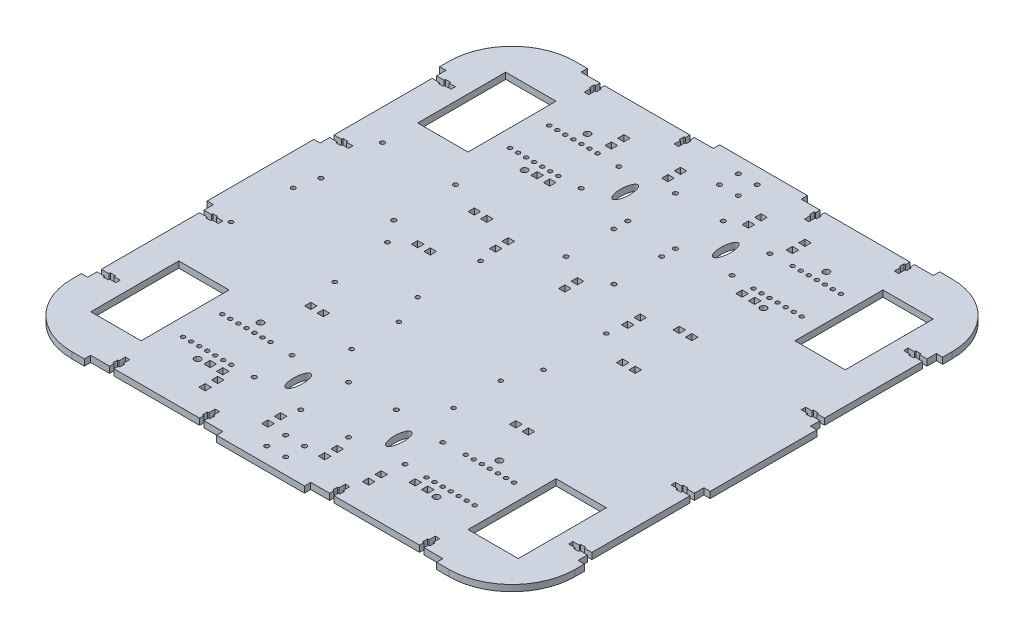
SolidWorks part; units mm, degrees
ref_plane "Front Plane" through (0, 0, 0) normal (0, 0, 1) x (1, 0, 0)
ref_plane "Top Plane" through (0, 0, 0) normal (0, 1, 0) x (1, 0, 0)
ref_plane "Right Plane" through (0, 0, 0) normal (1, 0, 0) x (0, 0, -1)
sketch "Sketch1" plane through (0, 0, 0) normal (0, 1, 0) x (1, 0, 0)
  line L0 (0, -1000) -> (0, 49000) construction
  line L1 (-170, 165) -> (-130, 165)
  line L2 (-170, 165) -> (-170, 95)
  line L3 (-170, 95) -> (-130, 95)
  line L4 (-130, 165) -> (-130, 95)
  line L5 (170, 95) -> (130, 95)
  line L6 (130, 165) -> (130, 95)
  line L7 (170, 165) -> (130, 165)
  line L8 (170, 165) -> (170, 95)
  line L9 (-1000, 0) -> (49000, 0) construction
  line L10 (-10, 190) -> (10, 190)
  line L11 (-10, 190) -> (-10, 170)
  line L12 (-10, 170) -> (10, 170)
  line L13 (10, 190) -> (10, 170)
  line L14 (-1010, 180) -> (48990, 180) construction
  line L15 (-1010, -180) -> (48990, -180) construction
  line L16 (0, 1000) -> (0, -49000) construction
  line L17 (-10, -170) -> (10, -170)
  line L18 (10, -190) -> (10, -170)
  line L19 (-10, -190) -> (10, -190)
  line L20 (-10, -190) -> (-10, -170)
  line L21 (170, -165) -> (170, -95)
  line L22 (-200, 200) -> (200, 200)
  line L23 (-200, 200) -> (-200, -200)
  line L24 (-200, -200) -> (200, -200)
  line L25 (200, 200) -> (200, -200)
  line L26 (170, -165) -> (130, -165)
  line L27 (130, -165) -> (130, -95)
  line L28 (170, -95) -> (130, -95)
  line L29 (-170, -95) -> (-130, -95)
  line L30 (-130, -165) -> (-130, -95)
  line L31 (-170, -165) -> (-130, -165)
  line L32 (-170, -165) -> (-170, -95)
  circle A0 centre (0, 0) radius 200 construction
  circle A1 centre (-7.5, 187.5) radius 1.75
  circle A2 centre (7.5, 187.5) radius 1.75
  circle A3 centre (7.5, 172.5) radius 1.75
  circle A4 centre (-7.5, 172.5) radius 1.75
  circle A5 centre (7.5, -187.5) radius 1.75
  circle A6 centre (-7.5, -187.5) radius 1.75
  circle A7 centre (-7.5, -172.5) radius 1.75
  circle A8 centre (7.5, -172.5) radius 1.75
  circle A9 centre (0, 0) radius 282.8427 construction
  point P8 (-150, 165)
  point P19 (0, 190)
  point P22 (-10, 180)
  dimension "D1" = 400
  dimension "D7" = 3.5
  dimension "D11" = 565.6854
  dimension "D2" = 40
  dimension "D3" = 70
  dimension "D4" = 150
  dimension "D5" = 20
  dimension "D6" = 180
  dimension "D8" = 2.5
  dimension "D9" = 2.5
  dimension "D10" = 35
extrude "Boss-Extrude2" add sketch "Sketch1" along normal blind 5 contours L25 L22 L23 L24 L1 L4 L3 L2 L7 L8 L5 L6 L10 L13 L12 L11 L19 L20 L17 L18 | L20 L19 L18 L17 A6 A5 A7 A8 | L13 L10 L11 L12 A2 A1 A3 A4 region at (0, 0, -180) region at (0, 0, 180) region at (0, 0, 0)
fillet "Fillet1" radius 50 4 edges at (200, 2.5, -200) (200, 2.5, 200) (-200, 2.5, 200) (-200, 2.5, -200)
sketch "Sketch2" plane through (0, 5, 0) normal (0, 1, 0) x (1, 0, 0)
  line L0 (-1094.0419, 130) -> (48905.9581, 130) construction
  line L1 (-130, 148.8) -> (-72.9, 148.8) construction
  line L2 (-130, 148.8) -> (-130, 111.2) construction
  line L3 (-130, 111.2) -> (-72.9, 111.2) construction
  line L4 (-72.9, 148.8) -> (-72.9, 111.2) construction
  line L5 (-130, 165) -> (-130, 95) construction
  line L6 (-170, 165) -> (-170, 95) construction
  line L7 (0, -1000) -> (0, 49000) construction
  line L8 (130, 111.2) -> (72.9, 111.2) construction
  line L9 (72.9, 148.8) -> (72.9, 111.2) construction
  line L10 (130, 148.8) -> (72.9, 148.8) construction
  line L11 (130, 148.8) -> (130, 111.2) construction
  line L12 (-1000, 0) -> (49000, 0) construction
  line L13 (130, -148.8) -> (130, -111.2) construction
  line L14 (130, -148.8) -> (72.9, -148.8) construction
  line L15 (72.9, -148.8) -> (72.9, -111.2) construction
  line L16 (130, -111.2) -> (72.9, -111.2) construction
  line L17 (-72.9, -148.8) -> (-72.9, -111.2) construction
  line L18 (-130, -111.2) -> (-72.9, -111.2) construction
  line L19 (-130, -148.8) -> (-130, -111.2) construction
  line L20 (-130, -148.8) -> (-72.9, -148.8) construction
  line L21 (-1094.0419, -130) -> (48905.9581, -130) construction
  circle A0 centre (-116, 145.6) radius 1.6
  circle A1 centre (-109.6, 145.6) radius 1.6
  circle A2 centre (-103.2, 145.6) radius 1.6
  circle A3 centre (-96.8, 145.6) radius 1.6
  circle A4 centre (-90.4, 145.6) radius 1.6
  circle A5 centre (-84, 145.6) radius 1.6
  circle A6 centre (-77.6, 145.6) radius 1.6
  circle A7 centre (-77.6, 114.4) radius 1.6
  circle A8 centre (-84, 114.4) radius 1.6
  circle A9 centre (-90.4, 114.4) radius 1.6
  circle A10 centre (-96.8, 114.4) radius 1.6
  circle A11 centre (-103.2, 114.4) radius 1.6
  circle A12 centre (-109.6, 114.4) radius 1.6
  circle A13 centre (-116, 114.4) radius 1.6
  circle A14 centre (77.6, 114.4) radius 1.6
  circle A15 centre (84, 114.4) radius 1.6
  circle A16 centre (90.4, 114.4) radius 1.6
  circle A17 centre (96.8, 114.4) radius 1.6
  circle A18 centre (103.2, 114.4) radius 1.6
  circle A19 centre (109.6, 114.4) radius 1.6
  circle A20 centre (116, 114.4) radius 1.6
  circle A21 centre (77.6, 145.6) radius 1.6
  circle A22 centre (84, 145.6) radius 1.6
  circle A23 centre (90.4, 145.6) radius 1.6
  circle A24 centre (96.8, 145.6) radius 1.6
  circle A25 centre (103.2, 145.6) radius 1.6
  circle A26 centre (109.6, 145.6) radius 1.6
  circle A27 centre (116, 145.6) radius 1.6
  circle A28 centre (116, -145.6) radius 1.6
  circle A29 centre (109.6, -145.6) radius 1.6
  circle A30 centre (103.2, -145.6) radius 1.6
  circle A31 centre (96.8, -145.6) radius 1.6
  circle A32 centre (90.4, -145.6) radius 1.6
  circle A33 centre (84, -145.6) radius 1.6
  circle A34 centre (77.6, -145.6) radius 1.6
  circle A35 centre (116, -114.4) radius 1.6
  circle A36 centre (109.6, -114.4) radius 1.6
  circle A37 centre (103.2, -114.4) radius 1.6
  circle A38 centre (96.8, -114.4) radius 1.6
  circle A39 centre (90.4, -114.4) radius 1.6
  circle A40 centre (84, -114.4) radius 1.6
  circle A41 centre (77.6, -114.4) radius 1.6
  circle A42 centre (-116, -114.4) radius 1.6
  circle A43 centre (-109.6, -114.4) radius 1.6
  circle A44 centre (-103.2, -114.4) radius 1.6
  circle A45 centre (-96.8, -114.4) radius 1.6
  circle A46 centre (-90.4, -114.4) radius 1.6
  circle A47 centre (-84, -114.4) radius 1.6
  circle A48 centre (-77.6, -114.4) radius 1.6
  circle A49 centre (-77.6, -145.6) radius 1.6
  circle A50 centre (-84, -145.6) radius 1.6
  circle A51 centre (-90.4, -145.6) radius 1.6
  circle A52 centre (-96.8, -145.6) radius 1.6
  circle A53 centre (-103.2, -145.6) radius 1.6
  circle A54 centre (-109.6, -145.6) radius 1.6
  circle A55 centre (-116, -145.6) radius 1.6
  point P9 (-130, 130)
  point P40 (-170, 130)
  dimension "D3" = 3.2
  dimension "D7" = 6.4
  dimension "D5" = 14
  dimension "D1" = 37.6
  dimension "D2" = 4.7
  dimension "D4" = 31.2
  dimension "D6" = 7
extrude "Cut-Extrude1" cut sketch "Sketch2" against normal blind 5
sketch "Sketch3" plane through (0, 5, 0) normal (0, 1, 0) x (1, 0, 0)
  line L0 (-150, -200) -> (150, -200) construction
  line L1 (-190, 3.34) -> (-88.4, 3.34) construction
  line L2 (-190, 3.34) -> (-190, -50) construction
  line L3 (-190, -50) -> (-88.4, -50) construction
  line L4 (-88.4, 3.34) -> (-88.4, -50) construction
  line L5 (-200, 150) -> (-200, -150) construction
  circle A0 centre (-176.03, -47.46) radius 1.65
  circle A1 centre (-174.76, 0.8) radius 1.65
  circle A2 centre (-93.48, -47.46) radius 1.65
  circle A3 centre (-99.83, 0.8) radius 1.65
  dimension "D5" = 3.3
  dimension "D8" = 3.3
  dimension "D9" = 96.52
  dimension "D10" = 90.17
  dimension "D1" = 101.6
  dimension "D2" = 53.34
  dimension "D3" = 13.97
  dimension "D4" = 2.54
  dimension "D6" = 15.24
  dimension "D7" = 50.8
  dimension "D11" = 150
  dimension "D12" = 10
extrude "Cut-Extrude2" cut sketch "Sketch3" against normal blind 10 contours A1 | A2 | L2 L1 L4 L3 | A0 | A3 region at (-174.76, 5, -0.8) region at (-93.48, 5, 47.46)
sketch "Sketch4" plane through (0, 5, 0) normal (0, 1, 0) x (1, 0, 0)
  line L0 (-19, 149) -> (19, 149) construction
  line L1 (-1149.7342, 130) -> (48850.2658, 130) construction
  line L2 (-22, 152) -> (22, 152) construction
  line L3 (-22, 152) -> (-22, 108) construction
  line L4 (-22, 108) -> (22, 108) construction
  line L5 (22, 152) -> (22, 108) construction
  line L6 (-19, 111) -> (19, 111) construction
  line L7 (-19, 100) -> (19, 100) construction
  line L8 (-1231.3219, 81) -> (48768.6781, 81) construction
  line L9 (-22, 103) -> (22, 103) construction
  line L10 (-22, 103) -> (-22, 59) construction
  line L11 (-22, 59) -> (22, 59) construction
  line L12 (22, 103) -> (22, 59) construction
  line L13 (-19, 62) -> (19, 62) construction
  line L14 (-19, -149) -> (19, -149) construction
  line L15 (-22, -152) -> (22, -152) construction
  line L16 (-130, 165) -> (-130, 95) construction
  line L17 (-150, 200) -> (150, 200) construction
  line L18 (22, -108) -> (22, -152) construction
  line L19 (-22, -108) -> (-22, -152) construction
  line L20 (-19, -111) -> (19, -111) construction
  line L21 (-22, -108) -> (22, -108) construction
  line L22 (-1022, -130) -> (48978, -130) construction
  line L23 (-130, -165) -> (-130, -95) construction
  circle A0 centre (-19, 149) radius 1.75
  circle A1 centre (19, 149) radius 1.75
  circle A2 centre (19, 111) radius 1.75
  circle A3 centre (-19, 111) radius 1.75
  circle A4 centre (-19, 100) radius 1.75
  circle A5 centre (19, 100) radius 1.75
  circle A6 centre (19, 62) radius 1.75
  circle A7 centre (-19, 62) radius 1.75
  circle A8 centre (-19, -149) radius 1.75
  circle A9 centre (19, -149) radius 1.75
  circle A10 centre (-19, -111) radius 1.75
  circle A11 centre (19, -111) radius 1.75
  point P9 (0, 149)
  point P10 (0, 152)
  point P14 (-22, 130)
  point P26 (0, 100)
  point P27 (0, 103)
  point P31 (-22, 81)
  point P38 (-130, 130)
  point P39 (0, 200)
  point P40 (0, 108)
  point P56 (-22, -130)
  point P58 (-130, -130)
  dimension "D1" = 3.5
  dimension "D5" = 3.5
  dimension "D2" = 38
  dimension "D3" = 44
  dimension "D4" = 38
  dimension "D6" = 38
  dimension "D7" = 44
  dimension "D8" = 38
  dimension "D9" = 5
  dimension "D10" = 2
extrude "Cut-Extrude3" cut sketch "Sketch4" against normal blind 10
sketch "Sketch5" plane through (0, 5, 0) normal (0, 1, 0) x (1, 0, 0)
  line L0 (-1136.3236, 43) -> (48863.6764, 43) construction
  line L1 (-174, 15) -> (-89, 15) construction
  line L2 (-174, 15) -> (-174, 71) construction
  line L3 (-174, 71) -> (-89, 71) construction
  line L4 (-89, 15) -> (-89, 71) construction
  line L5 (-180, 10) -> (-83, 10) construction
  line L6 (-180, 10) -> (-180, 76) construction
  line L7 (-180, 76) -> (-83, 76) construction
  line L8 (-83, 10) -> (-83, 76) construction
  line L9 (-200, 150) -> (-200, -150) construction
  line L10 (-150, -200) -> (150, -200) construction
  circle A0 centre (-170.5, 67.5) radius 1.75
  circle A1 centre (-112.5, 67.5) radius 1.75
  circle A2 centre (-112.5, 18.5) radius 1.75
  circle A3 centre (-170.5, 18.5) radius 1.75
  dimension "D4" = 3.5
  dimension "D5" = 3.5
  dimension "D1" = 56
  dimension "D2" = 85
  dimension "D3" = 58
  dimension "D6" = 3.5
  dimension "D7" = 49
  dimension "D8" = 3.5
  dimension "D9" = 5
  dimension "D10" = 5
  dimension "D11" = 6
  dimension "D12" = 6
  dimension "D13" = 20
  dimension "D14" = 210
extrude "Cut-Extrude4" cut sketch "Sketch5" against normal blind 10
sketch "Sketch6" plane through (0, 5, 0) normal (0, 1, 0) x (1, 0, 0)
  line L0 (-130, 165) -> (-130, 95) construction
  line L1 (0, -800) -> (0, 49200) construction
  line L2 (-150, 200) -> (150, 200) construction
  line L3 (-1200, 0) -> (48800, 0) construction
  line L4 (-200, 150) -> (-200, -150) construction
  ellipse E0 centre (-40, 130) end of major axis (-40, 140) minor radius 3.75
  ellipse E1 centre (40, 130) end of major axis (40, 140) minor radius 3.75
  ellipse E2 centre (40, -130) end of major axis (40, -140) minor radius 3.75
  ellipse E3 centre (-40, -130) end of major axis (-40, -140) minor radius 3.75
  point P13 (-130, 130)
  point P14 (-200, 0)
  point P26 (0, 200)
  dimension "D1" = 90
  dimension "D2" = 20
  dimension "D3" = 7.5
extrude "Cut-Extrude5" cut sketch "Sketch6" against normal blind 10
sketch "Sketch7" plane through (0, 5, 0) normal (0, 1, 0) x (1, 0, 0)
  line L0 (0, -1008.1082) -> (0, 48991.8918) construction
  line L1 (-53, 28) -> (53, 28) construction
  line L2 (-53, 28) -> (-53, -28) construction
  line L3 (-53, -28) -> (53, -28) construction
  line L4 (53, 28) -> (53, -28) construction
  line L5 (-53, 28) -> (-47, 28) construction
  line L6 (-53, 28) -> (-53, 22) construction
  line L7 (-53, 22) -> (-47, 22) construction
  line L8 (-47, 28) -> (-47, 22) construction
  line L9 (-1053, 0) -> (48947, 0) construction
  line L10 (-150, -200) -> (150, -200) construction
  line L11 (-200, 150) -> (-200, -150) construction
  circle A1 centre (-50, 25) radius 1.65
  circle A2 centre (50, 25) radius 1.65
  circle A3 centre (50, -25) radius 1.65
  circle A4 centre (-50, -25) radius 1.65
  point P10 (-50, 22)
  point P15 (-47, 25)
  point P16 (0, 28)
  point P17 (-53, 0)
  point P25 (0, -200)
  point P28 (-200, 0)
  dimension "D3" = 3.3
  dimension "D1" = 106
  dimension "D2" = 56
  dimension "D5" = 6
  dimension "D6" = 6
extrude "Cut-Extrude6" cut sketch "Sketch7" against normal blind 10
sketch "Sketch8" plane through (0, 5, 0) normal (0, 1, 0) x (1, 0, 0)
  line L0 (0, -1046.6714) -> (0, 48953.3286) construction
  line L1 (-43.5, -46.5) -> (43.5, -46.5) construction
  line L2 (-43.5, -46.5) -> (-43.5, -90) construction
  line L3 (-43.5, -90) -> (43.5, -90) construction
  line L4 (43.5, -46.5) -> (43.5, -90) construction
  line L5 (-43.5, -46.5) -> (-37.5, -46.5) construction
  line L6 (-43.5, -46.5) -> (-43.5, -52.5) construction
  line L7 (-43.5, -52.5) -> (-37.5, -52.5) construction
  line L8 (-37.5, -46.5) -> (-37.5, -52.5) construction
  line L9 (-1043.5, -68.25) -> (48956.5, -68.25) construction
  line L10 (37.5, -46.5) -> (37.5, -52.5) construction
  line L11 (43.5, -52.5) -> (37.5, -52.5) construction
  line L12 (-150, -200) -> (150, -200) construction
  circle A0 centre (-40.5, -49.5) radius 1.65
  circle A1 centre (40.5, -49.5) radius 1.65
  circle A2 centre (40.5, -87) radius 1.65
  circle A3 centre (-40.5, -87) radius 1.65
  point P10 (-40.5, -52.5)
  point P11 (-37.5, -49.5)
  point P15 (0, -46.5)
  point P17 (-43.5, -68.25)
  point P28 (0, -200)
  dimension "D3" = 3.3
  dimension "D1" = 87
  dimension "D2" = 6
  dimension "D4" = 43.5
  dimension "D5" = 110
extrude "Cut-Extrude7" cut sketch "Sketch8" against normal blind 5
sketch "Sketch10" plane through (0, 5, 0) normal (0, 1, 0) x (1, 0, 0)
  line L0 (-150, -200) -> (150, -200) construction
  line L1 (-125, -200) -> (-121.5, -200)
  line L2 (-125, -200) -> (-125, -191.5)
  line L3 (-125, -182.5) -> (-121.5, -182.5)
  line L4 (-121.5, -200) -> (-121.5, -191.5)
  line L6 (-121.5, -187.5) -> (-120.4, -187.5)
  line L7 (-126.1, -187.5) -> (-125, -187.5)
  line L8 (-126.1, -187.5) -> (-126.1, -191.5)
  line L9 (-126.1, -191.5) -> (-125, -191.5)
  line L10 (-120.4, -187.5) -> (-120.4, -191.5)
  line L11 (-121.5, -191.5) -> (-120.4, -191.5)
  line L12 (-125, -187.5) -> (-125, -182.5)
  line L13 (-121.5, -187.5) -> (-121.5, -182.5)
  line L14 (-125, -187.5) -> (-121.5, -187.5) construction
  line L15 (-121.5, -191.5) -> (-125, -191.5) construction
  line L16 (-53.5, -200) -> (-50, -200)
  line L17 (-50, -200) -> (-50, -191.5)
  line L18 (-50, -191.5) -> (-48.9, -191.5)
  line L19 (-48.9, -187.5) -> (-48.9, -191.5)
  line L20 (-50, -187.5) -> (-48.9, -187.5)
  line L21 (-50, -187.5) -> (-50, -182.5)
  line L22 (-53.5, -182.5) -> (-50, -182.5)
  line L23 (-53.5, -187.5) -> (-53.5, -182.5)
  line L24 (-54.6, -187.5) -> (-53.5, -187.5)
  line L25 (-54.6, -187.5) -> (-54.6, -191.5)
  line L26 (-54.6, -191.5) -> (-53.5, -191.5)
  line L27 (-53.5, -200) -> (-53.5, -191.5)
  line L28 (-50, -191.5) -> (-53.5, -191.5) construction
  line L29 (-53.5, -187.5) -> (-50, -187.5) construction
  line L30 (0, -1200) -> (0, 48800) construction
  line L31 (-200, 150) -> (-200, -150) construction
  line L32 (121.5, -191.5) -> (125, -191.5) construction
  line L33 (125, -187.5) -> (121.5, -187.5) construction
  line L34 (125, -200) -> (125, -191.5)
  line L35 (126.1, -191.5) -> (125, -191.5)
  line L36 (126.1, -187.5) -> (126.1, -191.5)
  line L37 (126.1, -187.5) -> (125, -187.5)
  line L38 (125, -187.5) -> (125, -182.5)
  line L39 (125, -182.5) -> (121.5, -182.5)
  line L40 (121.5, -187.5) -> (121.5, -182.5)
  line L41 (121.5, -187.5) -> (120.4, -187.5)
  line L42 (120.4, -187.5) -> (120.4, -191.5)
  line L43 (121.5, -191.5) -> (120.4, -191.5)
  line L44 (121.5, -200) -> (121.5, -191.5)
  line L45 (125, -200) -> (121.5, -200)
  line L46 (53.5, -187.5) -> (50, -187.5) construction
  line L47 (50, -191.5) -> (53.5, -191.5) construction
  line L48 (53.5, -200) -> (53.5, -191.5)
  line L49 (54.6, -191.5) -> (53.5, -191.5)
  line L50 (54.6, -187.5) -> (54.6, -191.5)
  line L51 (54.6, -187.5) -> (53.5, -187.5)
  line L52 (53.5, -187.5) -> (53.5, -182.5)
  line L53 (53.5, -182.5) -> (50, -182.5)
  line L54 (50, -187.5) -> (50, -182.5)
  line L55 (50, -187.5) -> (48.9, -187.5)
  line L56 (48.9, -187.5) -> (48.9, -191.5)
  line L57 (50, -191.5) -> (48.9, -191.5)
  line L58 (50, -200) -> (50, -191.5)
  line L59 (53.5, -200) -> (50, -200)
  line L60 (-1000, 0) -> (49000, 0) construction
  line L61 (125, 200) -> (121.5, 200)
  line L62 (121.5, 200) -> (121.5, 191.5)
  line L63 (121.5, 191.5) -> (120.4, 191.5)
  line L64 (120.4, 187.5) -> (120.4, 191.5)
  line L65 (121.5, 187.5) -> (120.4, 187.5)
  line L66 (121.5, 187.5) -> (121.5, 182.5)
  line L67 (125, 182.5) -> (121.5, 182.5)
  line L68 (125, 187.5) -> (125, 182.5)
  line L69 (126.1, 187.5) -> (125, 187.5)
  line L70 (126.1, 187.5) -> (126.1, 191.5)
  line L71 (126.1, 191.5) -> (125, 191.5)
  line L72 (125, 200) -> (125, 191.5)
  line L73 (53.5, 200) -> (50, 200)
  line L74 (50, 200) -> (50, 191.5)
  line L75 (50, 191.5) -> (48.9, 191.5)
  line L76 (48.9, 187.5) -> (48.9, 191.5)
  line L77 (50, 187.5) -> (48.9, 187.5)
  line L78 (50, 187.5) -> (50, 182.5)
  line L79 (53.5, 182.5) -> (50, 182.5)
  line L80 (53.5, 187.5) -> (53.5, 182.5)
  line L81 (54.6, 187.5) -> (53.5, 187.5)
  line L82 (54.6, 187.5) -> (54.6, 191.5)
  line L83 (54.6, 191.5) -> (53.5, 191.5)
  line L84 (53.5, 200) -> (53.5, 191.5)
  line L85 (-53.5, 200) -> (-53.5, 191.5)
  line L86 (-54.6, 191.5) -> (-53.5, 191.5)
  line L87 (-54.6, 187.5) -> (-54.6, 191.5)
  line L88 (-54.6, 187.5) -> (-53.5, 187.5)
  line L89 (-53.5, 187.5) -> (-53.5, 182.5)
  line L90 (-53.5, 182.5) -> (-50, 182.5)
  line L91 (-50, 187.5) -> (-50, 182.5)
  line L92 (-50, 187.5) -> (-48.9, 187.5)
  line L93 (-48.9, 187.5) -> (-48.9, 191.5)
  line L94 (-50, 191.5) -> (-48.9, 191.5)
  line L95 (-50, 200) -> (-50, 191.5)
  line L96 (-53.5, 200) -> (-50, 200)
  line L97 (-125, 200) -> (-125, 191.5)
  line L98 (-126.1, 191.5) -> (-125, 191.5)
  line L99 (-126.1, 187.5) -> (-126.1, 191.5)
  line L100 (-126.1, 187.5) -> (-125, 187.5)
  line L101 (-125, 187.5) -> (-125, 182.5)
  line L102 (-125, 182.5) -> (-121.5, 182.5)
  line L103 (-121.5, 187.5) -> (-121.5, 182.5)
  line L104 (-121.5, 187.5) -> (-120.4, 187.5)
  line L105 (-120.4, 187.5) -> (-120.4, 191.5)
  line L106 (-121.5, 191.5) -> (-120.4, 191.5)
  line L107 (-121.5, 200) -> (-121.5, 191.5)
  line L108 (-125, 200) -> (-121.5, 200)
  point P11 (-123.25, -200)
  point P15 (-123.25, -191.5)
  point P16 (-123.25, -187.5)
  point P17 (-123.25, -182.5)
  point P33 (0, -200)
  dimension "D1" = 3.5
  dimension "D2" = 5.7
  dimension "D3" = 5
  dimension "D4" = 4
  dimension "D5" = 1.1
  dimension "D7" = 75
  dimension "D8" = 50
  dimension "D9" = 17.5
  dimension "D6" = 2
extrude "Cut-Extrude8" cut sketch "Sketch10" against normal blind 10
sketch "Sketch11" plane through (0, 5, 0) normal (0, 1, 0) x (1, 0, 0)
  line L0 (-150, -200) -> (-125, -200) construction
  line L1 (-140.05, -200) -> (-34.95, -200)
  line L2 (-140.05, -200) -> (-140.05, -195)
  line L3 (-140.05, -195) -> (-34.95, -195)
  line L4 (-34.95, -200) -> (-34.95, -195)
  line L5 (-50, -200) -> (-50, -191.5) construction
  line L6 (-125, -191.5) -> (-125, -200) construction
  line L7 (0, -1200) -> (0, 48800) construction
  line L8 (-50, -200) -> (50, -200) construction
  line L9 (-1200, 0) -> (48800, 0) construction
  line L10 (-200, 150) -> (-200, -150) construction
  line L11 (140.05, -195) -> (34.95, -195)
  line L12 (34.95, -200) -> (34.95, -195)
  line L13 (140.05, -200) -> (34.95, -200)
  line L14 (140.05, -200) -> (140.05, -195)
  line L15 (140.05, 200) -> (140.05, 195)
  line L16 (140.05, 200) -> (34.95, 200)
  line L17 (34.95, 200) -> (34.95, 195)
  line L18 (140.05, 195) -> (34.95, 195)
  line L19 (-140.05, 195) -> (-34.95, 195)
  line L20 (-34.95, 200) -> (-34.95, 195)
  line L21 (-140.05, 200) -> (-34.95, 200)
  line L22 (-140.05, 200) -> (-140.05, 195)
  point P15 (0, -200)
  point P20 (-200, 0)
  dimension "D1" = 5
  dimension "D2" = 15.05
  dimension "D3" = 15.05
extrude "Cut-Extrude9" cut sketch "Sketch11" against normal blind 10
sketch "Sketch12" plane through (0, 5, 0) normal (0, 1, 0) x (1, 0, 0)
  line L0 (-200, 150) -> (-200, -150) construction
  line L1 (-200, 135) -> (-189, 135)
  line L2 (-200, 135) -> (-200, 131.5)
  line L3 (-200, 131.5) -> (-189, 131.5)
  line L4 (-180, 135) -> (-180, 131.5)
  line L5 (-200, 53.5) -> (-189, 53.5)
  line L6 (-189, 131.5) -> (-189, 130.4)
  line L7 (-189, 136.1) -> (-185, 136.1)
  line L8 (-189, 136.1) -> (-189, 135)
  line L9 (-189, 130.4) -> (-185, 130.4)
  line L10 (-185, 136.1) -> (-185, 135)
  line L11 (-185, 131.5) -> (-185, 130.4)
  line L12 (-185, 135) -> (-180, 135)
  line L13 (-185, 131.5) -> (-180, 131.5)
  line L14 (-189, 135) -> (-189, 131.5) construction
  line L15 (-185, 131.5) -> (-185, 135) construction
  line L16 (-189, 54.6) -> (-189, 53.5)
  line L17 (-189, 54.6) -> (-185, 54.6)
  line L18 (-185, 54.6) -> (-185, 53.5)
  line L19 (-185, 53.5) -> (-180, 53.5)
  line L20 (-180, 53.5) -> (-180, 50)
  line L21 (-185, 50) -> (-180, 50)
  line L22 (-185, 50) -> (-185, 48.9)
  line L23 (-189, 48.9) -> (-185, 48.9)
  line L24 (-189, 50) -> (-189, 48.9)
  line L25 (-200, 50) -> (-189, 50)
  line L26 (-200, 53.5) -> (-200, 50)
  line L27 (-1200, 0) -> (48800, 0) construction
  line L28 (-200, -53.5) -> (-200, -50)
  line L29 (-200, -50) -> (-189, -50)
  line L30 (-189, -50) -> (-189, -48.9)
  line L31 (-189, -48.9) -> (-185, -48.9)
  line L32 (-185, -50) -> (-185, -48.9)
  line L33 (-185, -50) -> (-180, -50)
  line L34 (-180, -53.5) -> (-180, -50)
  line L35 (-185, -53.5) -> (-180, -53.5)
  line L36 (-185, -54.6) -> (-185, -53.5)
  line L37 (-189, -54.6) -> (-185, -54.6)
  line L38 (-189, -54.6) -> (-189, -53.5)
  line L39 (-200, -53.5) -> (-189, -53.5)
  line L40 (-200, -135) -> (-200, -131.5)
  line L41 (-200, -131.5) -> (-189, -131.5)
  line L42 (-189, -131.5) -> (-189, -130.4)
  line L43 (-189, -130.4) -> (-185, -130.4)
  line L44 (-185, -131.5) -> (-185, -130.4)
  line L45 (-185, -131.5) -> (-180, -131.5)
  line L46 (-180, -135) -> (-180, -131.5)
  line L47 (-185, -135) -> (-180, -135)
  line L48 (-185, -136.1) -> (-185, -135)
  line L49 (-189, -136.1) -> (-185, -136.1)
  line L50 (-189, -136.1) -> (-189, -135)
  line L51 (-200, -135) -> (-189, -135)
  line L52 (0, -1200) -> (0, 48800) construction
  line L53 (-34.95, -200) -> (34.95, -200) construction
  line L54 (200, -135) -> (189, -135)
  line L55 (189, -136.1) -> (189, -135)
  line L56 (189, -136.1) -> (185, -136.1)
  line L57 (185, -136.1) -> (185, -135)
  line L58 (185, -135) -> (180, -135)
  line L59 (180, -135) -> (180, -131.5)
  line L60 (185, -131.5) -> (180, -131.5)
  line L61 (185, -131.5) -> (185, -130.4)
  line L62 (189, -130.4) -> (185, -130.4)
  line L63 (189, -131.5) -> (189, -130.4)
  line L64 (200, -131.5) -> (189, -131.5)
  line L65 (200, -135) -> (200, -131.5)
  line L66 (200, -53.5) -> (189, -53.5)
  line L67 (189, -54.6) -> (189, -53.5)
  line L68 (189, -54.6) -> (185, -54.6)
  line L69 (185, -54.6) -> (185, -53.5)
  line L70 (185, -53.5) -> (180, -53.5)
  line L71 (180, -53.5) -> (180, -50)
  line L72 (185, -50) -> (180, -50)
  line L73 (185, -50) -> (185, -48.9)
  line L74 (189, -48.9) -> (185, -48.9)
  line L75 (189, -50) -> (189, -48.9)
  line L76 (200, -50) -> (189, -50)
  line L77 (200, -53.5) -> (200, -50)
  line L78 (200, 53.5) -> (200, 50)
  line L79 (200, 50) -> (189, 50)
  line L80 (189, 50) -> (189, 48.9)
  line L81 (189, 48.9) -> (185, 48.9)
  line L82 (185, 50) -> (185, 48.9)
  line L83 (185, 50) -> (180, 50)
  line L84 (180, 53.5) -> (180, 50)
  line L85 (185, 53.5) -> (180, 53.5)
  line L86 (185, 54.6) -> (185, 53.5)
  line L87 (189, 54.6) -> (185, 54.6)
  line L88 (189, 54.6) -> (189, 53.5)
  line L89 (200, 53.5) -> (189, 53.5)
  line L90 (200, 135) -> (200, 131.5)
  line L91 (200, 131.5) -> (189, 131.5)
  line L92 (189, 131.5) -> (189, 130.4)
  line L93 (189, 130.4) -> (185, 130.4)
  line L94 (185, 131.5) -> (185, 130.4)
  line L95 (185, 131.5) -> (180, 131.5)
  line L96 (180, 135) -> (180, 131.5)
  line L97 (185, 135) -> (180, 135)
  line L98 (185, 136.1) -> (185, 135)
  line L99 (189, 136.1) -> (185, 136.1)
  line L100 (189, 136.1) -> (189, 135)
  line L101 (200, 135) -> (189, 135)
  point P31 (-200, 0)
  point P60 (0, -200)
  dimension "D1" = 20
  dimension "D2" = 3.5
  dimension "D3" = 5.7
  dimension "D4" = 5
  dimension "D5" = 4
  dimension "D6" = 15
  dimension "D7" = 1.1
  dimension "D9" = 50
  dimension "D8" = 2
extrude "Cut-Extrude10" cut sketch "Sketch12" against normal blind 5
sketch "Sketch13" plane through (0, 5, 0) normal (0, 1, 0) x (1, 0, 0)
  line L0 (-200, 150) -> (-200, 135) construction
  line L1 (-200, 142.5) -> (-195, 142.5)
  line L2 (-200, 142.5) -> (-200, 42.4)
  line L3 (-200, 42.4) -> (-195, 42.4)
  line L4 (-195, 142.5) -> (-195, 42.4)
  line L6 (-200, 50) -> (-189, 50) construction
  line L7 (-1200, 0) -> (48800, 0) construction
  line L8 (-200, 50) -> (-200, -50) construction
  line L9 (0, -800) -> (0, 49200) construction
  line L10 (-34.95, 200) -> (34.95, 200) construction
  line L11 (-200, -42.4) -> (-195, -42.4)
  line L12 (-195, -142.5) -> (-195, -42.4)
  line L13 (-200, -142.5) -> (-195, -142.5)
  line L14 (-200, -142.5) -> (-200, -42.4)
  line L15 (0, 800) -> (0, -49200) construction
  line L16 (200, -142.5) -> (200, -42.4)
  line L17 (200, -142.5) -> (195, -142.5)
  line L18 (195, -142.5) -> (195, -42.4)
  line L19 (200, -42.4) -> (195, -42.4)
  line L20 (200, 42.4) -> (195, 42.4)
  line L21 (195, 142.5) -> (195, 42.4)
  line L22 (200, 142.5) -> (195, 142.5)
  line L23 (200, 142.5) -> (200, 42.4)
  point P13 (-200, 0)
  point P18 (0, 200)
  dimension "D1" = 7.6
  dimension "D2" = 5
extrude "Cut-Extrude11" cut sketch "Sketch13" against normal blind 5
sketch "Sketch14" plane through (0, 5, 0) normal (0, 1, 0) x (1, 0, 0)
  line L0 (34, 164) -> (29, 164)
  line L1 (34, 154) -> (29, 154)
  line L2 (34, 154) -> (34, 159)
  line L3 (34, 159) -> (29, 159)
  line L4 (29, 154) -> (29, 159)
  line L5 (34, 164) -> (34, 169)
  line L6 (34, 169) -> (29, 169)
  line L7 (29, 164) -> (29, 169)
  line L8 (69, 164) -> (64, 164)
  line L9 (69, 154) -> (64, 154)
  line L10 (69, 154) -> (69, 159)
  line L11 (69, 159) -> (64, 159)
  line L12 (64, 154) -> (64, 159)
  line L13 (69, 164) -> (69, 169)
  line L14 (69, 169) -> (64, 169)
  line L15 (64, 164) -> (64, 169)
  line L16 (5, 47) -> (0, 47)
  line L17 (5, 37) -> (0, 37)
  line L18 (5, 37) -> (5, 42)
  line L19 (5, 42) -> (0, 42)
  line L20 (0, 37) -> (0, 42)
  line L21 (5, 47) -> (5, 52)
  line L22 (5, 52) -> (0, 52)
  line L23 (0, 47) -> (0, 52)
  line L24 (55, 47) -> (50, 47)
  line L25 (55, 37) -> (50, 37)
  line L26 (55, 37) -> (55, 42)
  line L27 (55, 42) -> (50, 42)
  line L28 (50, 37) -> (50, 42)
  line L29 (55, 47) -> (55, 52)
  line L30 (55, 52) -> (50, 52)
  line L31 (50, 47) -> (50, 52)
  line L32 (25, -164) -> (20, -164)
  line L33 (25, -174) -> (20, -174)
  line L34 (25, -174) -> (25, -169)
  line L35 (25, -169) -> (20, -169)
  line L36 (20, -174) -> (20, -169)
  line L37 (25, -164) -> (25, -159)
  line L38 (25, -159) -> (20, -159)
  line L39 (20, -164) -> (20, -159)
  line L40 (60, -164) -> (55, -164)
  line L41 (60, -174) -> (55, -174)
  line L42 (60, -174) -> (60, -169)
  line L43 (60, -169) -> (55, -169)
  line L44 (55, -174) -> (55, -169)
  line L45 (60, -164) -> (60, -159)
  line L46 (60, -159) -> (55, -159)
  line L47 (55, -164) -> (55, -159)
  line L48 (-30, 164) -> (-35, 164)
  line L49 (-30, 154) -> (-35, 154)
  line L50 (-30, 154) -> (-30, 159)
  line L51 (-30, 159) -> (-35, 159)
  line L52 (-35, 154) -> (-35, 159)
  line L53 (-30, 164) -> (-30, 169)
  line L54 (-30, 169) -> (-35, 169)
  line L55 (-35, 164) -> (-35, 169)
  line L56 (-50, 47) -> (-55, 47)
  line L57 (-50, 37) -> (-55, 37)
  line L58 (-50, 37) -> (-50, 42)
  line L59 (-50, 42) -> (-55, 42)
  line L60 (-55, 37) -> (-55, 42)
  line L61 (-50, 47) -> (-50, 52)
  line L62 (-50, 52) -> (-55, 52)
  line L63 (-55, 47) -> (-55, 52)
  line L64 (-20, -164) -> (-25, -164)
  line L65 (-20, -174) -> (-25, -174)
  line L66 (-20, -174) -> (-20, -169)
  line L67 (-20, -169) -> (-25, -169)
  line L68 (-25, -174) -> (-25, -169)
  line L69 (-20, -164) -> (-20, -159)
  line L70 (-20, -159) -> (-25, -159)
  line L71 (-25, -164) -> (-25, -159)
  line L72 (19, 62) -> (-19, 62) construction
  line L73 (19, 149) -> (-19, 149) construction
  line L74 (-75, 164) -> (-80, 164)
  line L75 (-75, 154) -> (-80, 154)
  line L76 (-75, 154) -> (-75, 159)
  line L77 (-75, 159) -> (-80, 159)
  line L78 (-80, 154) -> (-80, 159)
  line L79 (-75, 164) -> (-75, 169)
  line L80 (-75, 169) -> (-80, 169)
  line L81 (-80, 164) -> (-80, 169)
  line L82 (19, -149) -> (-19, -149) construction
  line L83 (-70, -164) -> (-75, -164)
  line L84 (-70, -174) -> (-75, -174)
  line L85 (-70, -174) -> (-70, -169)
  line L86 (-70, -169) -> (-75, -169)
  line L87 (-75, -174) -> (-75, -169)
  line L88 (-70, -164) -> (-70, -159)
  line L89 (-70, -159) -> (-75, -159)
  line L90 (-75, -164) -> (-75, -159)
  line L91 (79, -156) -> (74, -156)
  line L92 (89, -156) -> (84, -156)
  line L93 (89, -156) -> (89, -151)
  line L94 (89, -151) -> (84, -151)
  line L95 (84, -156) -> (84, -151)
  line L96 (79, -156) -> (79, -151)
  line L97 (79, -151) -> (74, -151)
  line L98 (74, -156) -> (74, -151)
  line L99 (79, -76) -> (74, -76)
  line L100 (89, -76) -> (84, -76)
  line L101 (89, -76) -> (89, -71)
  line L102 (89, -71) -> (84, -71)
  line L103 (84, -76) -> (84, -71)
  line L104 (79, -76) -> (79, -71)
  line L105 (79, -71) -> (74, -71)
  line L106 (74, -76) -> (74, -71)
  line L107 (79, 9) -> (74, 9)
  line L108 (89, 9) -> (84, 9)
  line L109 (89, 9) -> (89, 14)
  line L110 (89, 14) -> (84, 14)
  line L111 (84, 9) -> (84, 14)
  line L112 (79, 9) -> (79, 14)
  line L113 (79, 14) -> (74, 14)
  line L114 (74, 9) -> (74, 14)
  line L115 (79, 54) -> (74, 54)
  line L116 (89, 54) -> (84, 54)
  line L117 (89, 54) -> (89, 59)
  line L118 (89, 59) -> (84, 59)
  line L119 (84, 54) -> (84, 59)
  line L120 (79, 54) -> (79, 59)
  line L121 (79, 59) -> (74, 59)
  line L122 (74, 54) -> (74, 59)
  line L123 (79, 104) -> (74, 104)
  line L124 (89, 104) -> (84, 104)
  line L125 (89, 104) -> (89, 109)
  line L126 (89, 109) -> (84, 109)
  line L127 (84, 104) -> (84, 109)
  line L128 (79, 104) -> (79, 109)
  line L129 (79, 109) -> (74, 109)
  line L130 (74, 104) -> (74, 109)
  line L131 (0, -1200) -> (0, 48800) construction
  line L132 (-34.95, -200) -> (34.95, -200) construction
  line L133 (-79, 104) -> (-79, 109)
  line L134 (-79, 109) -> (-74, 109)
  line L135 (-74, 104) -> (-74, 109)
  line L136 (-79, 104) -> (-74, 104)
  line L137 (-89, 104) -> (-89, 109)
  line L138 (-89, 109) -> (-84, 109)
  line L139 (-84, 104) -> (-84, 109)
  line L140 (-89, 104) -> (-84, 104)
  line L141 (-79, 54) -> (-79, 59)
  line L142 (-79, 59) -> (-74, 59)
  line L143 (-74, 54) -> (-74, 59)
  line L144 (-79, 54) -> (-74, 54)
  line L145 (-89, 54) -> (-89, 59)
  line L146 (-89, 59) -> (-84, 59)
  line L147 (-84, 54) -> (-84, 59)
  line L148 (-89, 54) -> (-84, 54)
  line L149 (-79, 9) -> (-79, 14)
  line L150 (-79, 14) -> (-74, 14)
  line L151 (-74, 9) -> (-74, 14)
  line L152 (-79, 9) -> (-74, 9)
  line L153 (-89, 9) -> (-89, 14)
  line L154 (-89, 14) -> (-84, 14)
  line L155 (-84, 9) -> (-84, 14)
  line L156 (-89, 9) -> (-84, 9)
  line L157 (-79, -76) -> (-79, -71)
  line L158 (-79, -71) -> (-74, -71)
  line L159 (-74, -76) -> (-74, -71)
  line L160 (-79, -76) -> (-74, -76)
  line L161 (-89, -76) -> (-89, -71)
  line L162 (-89, -71) -> (-84, -71)
  line L163 (-84, -76) -> (-84, -71)
  line L164 (-89, -76) -> (-84, -76)
  line L165 (-79, -156) -> (-79, -151)
  line L166 (-79, -151) -> (-74, -151)
  line L167 (-74, -156) -> (-74, -151)
  line L168 (-79, -156) -> (-74, -156)
  line L169 (-89, -156) -> (-89, -151)
  line L170 (-89, -151) -> (-84, -151)
  line L171 (-84, -156) -> (-84, -151)
  line L172 (-89, -156) -> (-84, -156)
  circle A0 centre (19, 149) radius 1.75 construction
  point P78 (0, 49.5)
  point P79 (0, 62)
  point P83 (0, 149)
  point P84 (0, -149)
  point P151 (0, -200)
  dimension "D20" = 10
  dimension "D1" = 5
  dimension "D2" = 5
  dimension "D3" = 5
  dimension "D4" = 5
  dimension "D5" = 5
  dimension "D6" = 5
  dimension "D7" = 5
  dimension "D8" = 5
  dimension "D9" = 5
  dimension "D10" = 5
  dimension "D11" = 5
  dimension "D12" = 5
  dimension "D13" = 5
  dimension "D14" = 5
  dimension "D15" = 5
  dimension "D16" = 5
  dimension "D17" = 5
  dimension "D18" = 5
  dimension "D19" = 30
  dimension "D21" = 10
  dimension "D22" = 10
  dimension "D23" = 45
  dimension "D24" = 50
  dimension "D25" = 30
  dimension "D26" = 5
  dimension "D27" = 5
  dimension "D28" = 40
  dimension "D29" = 20
  dimension "D30" = 10
  dimension "D31" = 30
  dimension "D32" = 20
  dimension "D33" = 5
  dimension "D34" = 5
  dimension "D35" = 45
  dimension "D36" = 5
  dimension "D37" = 5
  dimension "D38" = 5
  dimension "D39" = 5
  dimension "D40" = 5
  dimension "D41" = 5
  dimension "D42" = 5
  dimension "D43" = 5
  dimension "D44" = 5
  dimension "D45" = 5
  dimension "D46" = 5
  dimension "D47" = 45
  dimension "D48" = 45
  dimension "D49" = 40
  dimension "D50" = 80
  dimension "D51" = 75
extrude "Cut-Extrude12" cut sketch "Sketch14" against normal blind 10
sketch "Sketch15" plane through (0, 5, 0) normal (0, 1, 0) x (1, 0, 0)
  line L0 (-1130, 130) -> (48870, 130) construction
  line L1 (-130, 165) -> (-130, 95) construction
  line L2 (0, -800) -> (0, 49200) construction
  line L3 (-34.95, 200) -> (34.95, 200) construction
  line L4 (-1200, 0) -> (48800, 0) construction
  line L5 (-200, 42.4) -> (-200, -42.4) construction
  line L6 (1200, 0) -> (-48800, 0) construction
  circle A0 centre (-95, 105) radius 2.5
  circle A1 centre (-95, 155) radius 2.5
  circle A2 centre (95, 155) radius 2.5
  circle A3 centre (95, 105) radius 2.5
  circle A4 centre (95, -105) radius 2.5
  circle A5 centre (95, -155) radius 2.5
  circle A6 centre (-95, -155) radius 2.5
  circle A7 centre (-95, -105) radius 2.5
  point P7 (-130, 130)
  point P14 (0, 200)
  point P19 (-200, 0)
  dimension "D1" = 5
  dimension "D2" = 25
  dimension "D3" = 35
extrude "Cut-Extrude13" cut sketch "Sketch15" against normal blind 10
sketch "Sketch16" plane through (0, 5, 0) normal (0, 1, 0) x (1, 0, 0)
  line L1 (-60, 145) -> (-60, 115) construction
  line L2 (-130, 165) -> (-130, 95) construction
  line L3 (0, -800) -> (0, 49200) construction
  line L4 (-34.95, 200) -> (34.95, 200) construction
  line L5 (-1200, 0) -> (48800, 0) construction
  line L6 (-200, 42.4) -> (-200, -42.4) construction
  circle A0 centre (-60, 145) radius 1.75
  circle A1 centre (-60, 115) radius 1.75
  circle A2 centre (60, 115) radius 1.75
  circle A3 centre (60, 145) radius 1.75
  circle A4 centre (60, -115) radius 1.75
  circle A5 centre (60, -145) radius 1.75
  circle A6 centre (-60, -145) radius 1.75
  circle A7 centre (-60, -115) radius 1.75
  ellipse E0 centre (-40, 130) end of major axis (-40, 140) minor radius 3.75 construction
  point P10 (-130, 130)
  point P13 (-60, 130)
  point P19 (0, 200)
  point P24 (-200, 0)
  dimension "D1" = 3.5
  dimension "D2" = 30
  dimension "D3" = 20
extrude "Cut-Extrude14" cut sketch "Sketch16" against normal blind 10
